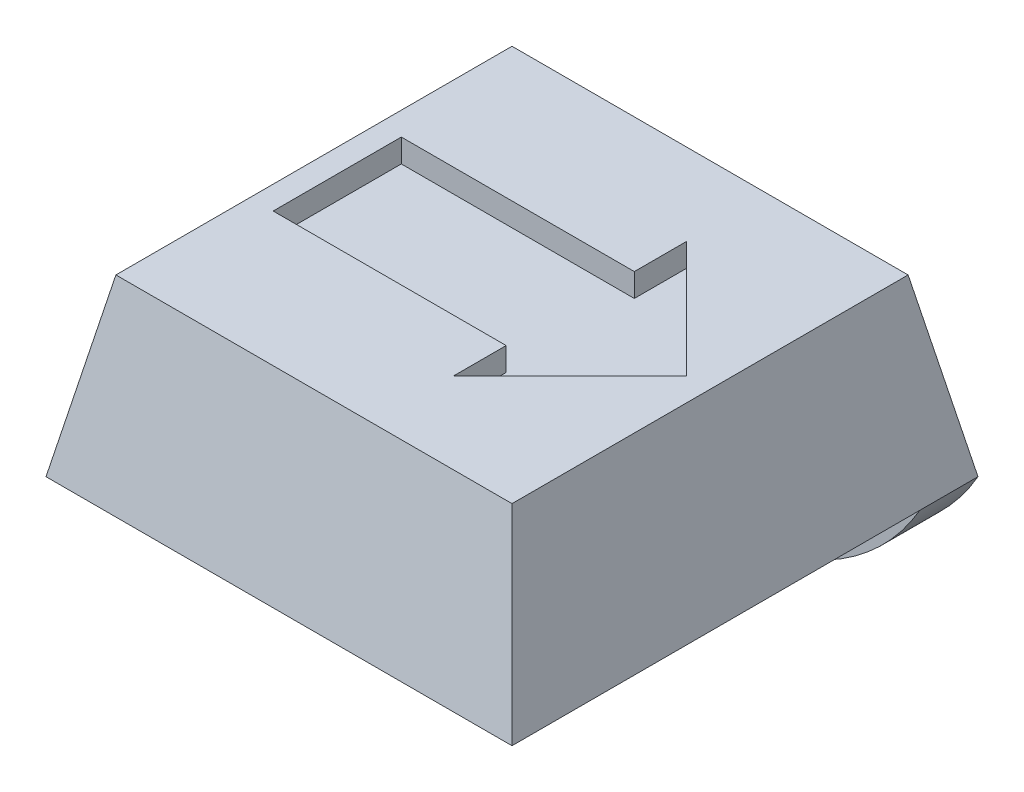
SolidWorks part; units mm, degrees
ref_plane "Front Plane" through (0, 0, 0) normal (0, 0, 1) x (1, 0, 0)
ref_plane "Top Plane" through (0, 0, 0) normal (0, 1, 0) x (1, 0, 0)
ref_plane "Right Plane" through (0, 0, 0) normal (1, 0, 0) x (0, 0, -1)
sketch "Sketch1" plane through (0, 0, 0) normal (0, 1, 0) x (1, 0, 0)
  line L1 (0, 0) -> (8, 0)
  line L2 (0, 0) -> (0, 8)
  line L3 (0, 8) -> (8, 8)
  line L4 (8, 0) -> (8, 8)
  dimension "D1" = 8
  dimension "D2" = 8
extrude "Boss-Extrude1" add sketch "Sketch1" along normal blind 3
sketch "Sketch2" plane through (0, 0, 0) normal (0, 0, 1) x (1, 0, 0)
  line L0 (0, 0) -> (0.6, 3)
  line L1 (0, 3) -> (8, 3) construction
  line L2 (0.6, 3) -> (0, 3)
  line L3 (0, 3) -> (0, 0)
  line L4 (8, 0) -> (7.4, 3)
  line L5 (7.4, 3) -> (8, 3)
  line L6 (8, 3) -> (8, 0)
  dimension "D1" = 0.6
  dimension "D2" = 0.6
extrude "Cut-Extrude1" cut sketch "Sketch2" against normal through all both and the other way through all
sketch "Sketch3" plane through (0, 0, 0) normal (1, 0, 0) x (0, 0, -1)
  line L0 (0, 0) -> (0.6, 3)
  line L1 (8, 3) -> (0, 3) construction
  line L2 (0.6, 3) -> (0, 3)
  line L3 (0, 3) -> (0, 0)
  line L4 (8, 3) -> (7.4, 3)
  line L5 (7.4, 3) -> (8, 0)
  line L6 (8, 3) -> (8, 0)
  dimension "D1" = 0.6
  dimension "D2" = 0.6
extrude "Cut-Extrude2" cut sketch "Sketch3" along normal blind 11
sketch "Sketch4" plane through (0, 0, 0) normal (0, -1, 0) x (1, 0, 0)
  line L0 (8, 0) -> (8, -8) construction
  line L3 (0, 0) -> (8, 0) construction
  circle A0 centre (4, -3.75) radius 1.75
  dimension "D1" = 3.5
  dimension "D2" = 4
  dimension "D3" = 3.75
extrude "Cut-Extrude3" cut sketch "Sketch4" against normal blind 0.4
sketch "Sketch5" plane through (0, 0, 0) normal (0, -1, 0) x (1, 0, 0)
  line L0 (8, 0) -> (8, -8) construction
  line L1 (0, -8) -> (8, -8)
  line L2 (0, -8) -> (0, -7)
  line L3 (0, -7) -> (8, -7)
  line L4 (8, -8) -> (8, -7)
  dimension "D1" = 1
extrude "Boss-Extrude2" add sketch "Sketch5" along normal blind 2
fillet "Fillet1" radius 4 2 edges at (8, -2, -7.5) (0, -2, -7.5)
sketch "Sketch6" plane through (0, 3, 0) normal (0, 1, 0) x (1, 0, 0)
  line L0 (5, 5.1) -> (5, 6)
  line L1 (1, 5.1) -> (5, 5.1)
  line L2 (1, 5.1) -> (1, 2.9)
  line L3 (1, 2.9) -> (5, 2.9)
  line L4 (5, 5.1) -> (5, 2.9)
  line L5 (5, 6) -> (7, 4)
  line L6 (7, 4) -> (5, 2)
  line L7 (5, 2) -> (5, 2.9)
  line L8 (7.4, 7.4) -> (0.6, 7.4) construction
  line L9 (7.4, 0.6) -> (0.6, 0.6) construction
  line L10 (7.4, 7.4) -> (7.4, 0.6) construction
  line L11 (0.6, 7.4) -> (0.6, 0.6) construction
  point P16 (7.4, 4)
  dimension "D1" = 2.3
  dimension "D2" = 2.3
  dimension "D3" = 1.4
  dimension "D4" = 1.4
  dimension "D5" = 0.4
  dimension "D6" = 0.4
  dimension "D7" = 4
  dimension "D8" = 0
extrude "Cut-Extrude4" cut sketch "Sketch6" against normal blind 0.4 contours L4 L1 L2 L3 | L7 L6 L5 L0 L4 region at (3, 3, -4) region at (5.6667, 3, -4)
